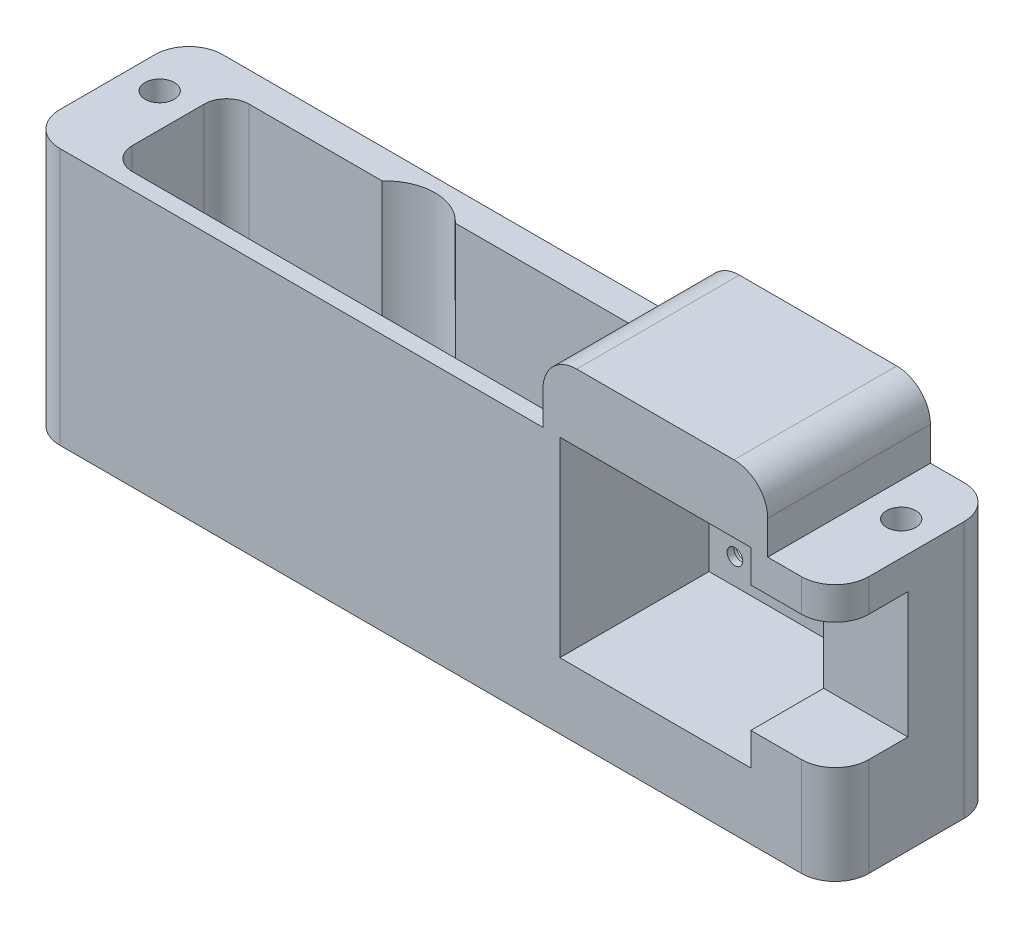
SolidWorks part; units mm, degrees
ref_plane "Front Plane" through (0, 0, 0) normal (0, 0, 1) x (1, 0, 0)
ref_plane "Top Plane" through (0, 0, 0) normal (0, 1, 0) x (1, 0, 0)
ref_plane "Right Plane" through (0, 0, 0) normal (1, 0, 0) x (0, 0, -1)
sketch "Sketch1" plane through (0, 0, 0) normal (0, 0, 1) x (1, 0, 0)
  line L1 (-90, 28.6) -> (90, 28.6)
  line L2 (-90, 28.6) -> (-90, -28.6)
  line L3 (-90, -28.6) -> (90, -28.6)
  line L4 (90, 28.6) -> (90, -28.6)
  line L5 (-90, 28.6) -> (90, -28.6) construction
  line L6 (-90, -28.6) -> (90, 28.6) construction
  line L7 (25, 28.6) -> (75, 28.6)
  line L8 (25, 28.6) -> (25, 43.6)
  line L9 (25, 43.6) -> (75, 43.6)
  line L10 (75, 28.6) -> (75, 43.6)
  point P0 (0, 0)
  dimension "D1" = 180
  dimension "D2" = 57.2
  dimension "D3" = 15
  dimension "D4" = 15
  dimension "D5" = 50
extrude "Boss-Extrude1" add sketch "Sketch1" along normal blind 36.2 contours L4 L1 L2 L3 | L1 L10 L9 L8 region at (0, 0, 0) region at (50, 36.1, 0)
sketch "Sketch2" plane through (0, -28.6, 0) normal (0, -1, 0) x (1, 0, 0)
  line L0 (-90, 36.2) -> (-90, 0) construction
  line L1 (-90, 0) -> (90, 0) construction
  line L3 (-82.5, 14) -> (82.5, 14) construction
  line L4 (-37.9069, 8.3431) -> (-26.5931, 8.3431) construction
  line L5 (-37.9069, 8.3431) -> (-37.9069, 19.6569) construction
  line L6 (-37.9069, 19.6569) -> (-26.5931, 19.6569) construction
  line L7 (-26.5931, 8.3431) -> (-26.5931, 19.6569) construction
  line L8 (-37.9069, 8.3431) -> (-26.5931, 19.6569) construction
  line L9 (-37.9069, 19.6569) -> (-26.5931, 8.3431) construction
  circle A0 centre (-82.5, 14) radius 3.25
  circle A1 centre (82.5, 14) radius 3.25
  circle A2 centre (-32.25, 14) radius 5.75
  circle A3 centre (-32.25, 14) radius 11
  circle A4 centre (-37.9069, 19.6569) radius 1.75
  circle A5 centre (-26.5931, 19.6569) radius 1.75
  circle A6 centre (-26.5931, 8.3431) radius 1.75
  circle A7 centre (-37.9069, 8.3431) radius 1.75
  dimension "D1" = 6.5
  dimension "D4" = 6.5
  dimension "D7" = 11.5
  dimension "D8" = 22
  dimension "D9" = 3.5
  dimension "D11" = 50.25
  dimension "D2" = 7.5
  dimension "D3" = 14
  dimension "D5" = 14
  dimension "D6" = 114.75
  dimension "D10" = 8
extrude "Cut-Extrude1" cut sketch "Sketch2" against normal up to surface (57.2 mm away) contours A0 | A2 | A4 | A5 | A7 | A6 | A1 region at (-82.5, -28.6, 14) region at (-32.25, -28.6, 14) up to face at (-32.5, 28.6, 18.1)
fillet "Fillet1" radius 7.5 4 edges at (90, 0, 0) (90, 0, 36.2) (-90, 0, 0) (-90, 0, 36.2)
sketch "Sketch3" plane through (0, 28.6, 0) normal (0, 1, 0) x (1, 0, 0)
  line L0 (-82.5, -36.2) -> (25, -36.2) construction
  line L1 (-70, -6.5931) -> (25, -6.5931)
  line L2 (-75, -11.5931) -> (-75, -27.6)
  line L3 (-70, -32.6) -> (25, -32.6)
  line L4 (25, -6.5931) -> (25, -32.6)
  line L5 (25, -36.2) -> (25, 0) construction
  circle A0 centre (-37.9069, -8.3431) radius 1.75 construction
  circle A1 centre (-82.5, -14) radius 3.25 construction
  arc A2 (-75, -27.6) -> (-70, -32.6) centre (-70, -27.6) ccw
  arc A3 (-70, -6.5931) -> (-75, -11.5931) centre (-70, -11.5931) ccw
  circle A4 centre (-32.25, -14) radius 11
  circle M6 centre (-26.5931, -8.3431) radius 1.75
  circle M7 centre (-37.9069, -19.6569) radius 1.75
  circle M8 centre (-32.25, -14) radius 5.75
  circle M9 centre (-26.5931, -19.6569) radius 1.75
  circle M10 centre (-37.9069, -8.3431) radius 1.75
  line M16 (25, -36.2) -> (25, 0)
  dimension "D4" = 5
  dimension "D5" = 22
  dimension "D1" = 26.0069
  dimension "D2" = 3.6
  dimension "D3" = 7.5
extrude "Cut-Extrude3" cut sketch "Sketch3" against normal offset from surface (52.2 mm away) 5 contours L1 A4 | L1 A4 M6 M10 M7 M9 M8 | A4 L1 A3 L2 A2 L3 M16 region at (-55.1913, 28.6, 7.6264) region at (-32.25, 28.6, 5.1337) region at (-39.1447, 28.6, 6.88) up to face at (-82.5, -28.6, 10.75)
sketch "Sketch4" plane through (0, 0, 36.2) normal (0, 0, 1) x (1, 0, 0)
  line L0 (-82.5, 28.6) -> (25, 28.6) construction
  line L1 (28.75, 28.6) -> (71.25, 28.6)
  line L2 (28.75, 28.6) -> (28.75, -13.9)
  line L3 (28.75, -13.9) -> (71.25, -13.9)
  line L4 (71.25, 28.6) -> (71.25, -13.9)
  line L5 (50, 7.35) -> (75, 28.6) construction
  line L6 (50, 7.35) -> (25, 28.6) construction
  line L7 (28.75, 7.35) -> (71.25, 7.35) construction
  line L8 (34.5, 22.85) -> (65.5, -8.15) construction
  line L9 (34.5, 22.85) -> (34.5, -8.15) construction
  circle A0 centre (50, 7.35) radius 11.25
  circle A5 centre (34.5, 22.85) radius 1.75
  circle A6 centre (65.5, 22.85) radius 1.75
  circle A7 centre (65.5, -8.15) radius 1.75
  circle A8 centre (34.5, -8.15) radius 1.75
  dimension "D5" = 22.5
  dimension "D6" = 3.5
  dimension "D3" = 2
  dimension "D7" = 31
  dimension "D8" = 31
  dimension "D1" = 42.5
  dimension "D2" = 42.5
  dimension "D4" = 2
extrude "Cut-Extrude4" cut sketch "Sketch4" against normal blind 33.2
extrude "Cut-Extrude5" cut sketch "Sketch4<3>" against normal up to surface (36.2 mm away) contours A5 | A0 | A8 | A7 | A6 up to face at (25, 18.05, 0)
sketch "Sketch4<3>" plane through (0, 0, 36.2) normal (0, 0, 1) x (1, 0, 0) same geometry as "Sketch4"
fillet "Fillet2" radius 7.5 2 edges at (75, 43.6, 18.1) (25, 43.6, 18.1)
sketch "Sketch8" plane through (0, 0, 0) normal (0, 0, -1) x (-1, 0, 0)
  circle A0 centre (-65.5, 22.85) radius 3
  circle A1 centre (-34.5, 22.85) radius 3
  circle A2 centre (-34.5, -8.15) radius 3
  circle A3 centre (-65.5, -8.15) radius 3
  circle A4 centre (-34.5, -8.15) radius 1.75 construction
  circle A5 centre (-65.5, -8.15) radius 1.75 construction
  circle A6 centre (-65.5, 22.85) radius 1.75 construction
  dimension "D1" = 6
extrude "Cut-Extrude8" cut sketch "Sketch8" against normal blind 1.5
sketch "Sketch7" plane through (0, 0, 36.2) normal (0, 0, 1) x (1, 0, 0)
  line L0 (71.25, 28.6) -> (28.75, 28.6) construction
  line L2 (50, 36.1) -> (50, -21.4) construction
  line L4 (28.75, 7.35) -> (71.25, 7.35) construction
  line L5 (28.75, 28.6) -> (28.75, -13.9) construction
  line L6 (71.25, -13.9) -> (71.25, 28.6) construction
  circle A0 centre (50, -21.4) radius 3.25
  circle A1 centre (50, 36.1) radius 3.25
  point P6 (50, -21.4)
  point P8 (50, 7.35)
  dimension "D1" = 6.5
  dimension "D4" = 6.5
  dimension "D2" = 7.5
extrude "Cut-Extrude7" cut sketch "Sketch7" against normal up to surface (36.2 mm away) up to face at (62.5, -8.15, 0)
extrude "Boss-Extrude3" add sketch "Sketch7<2>" against normal blind 22.4
sketch "Sketch7<2>" plane through (0, 0, 36.2) normal (0, 0, 1) x (1, 0, 0) same geometry as "Sketch7"
sketch "Sketch9" plane through (90, 0, 0) normal (1, 0, 0) x (0, 0, -1)
  line L0 (-36.2, -28.6) -> (-36.2, 28.6) construction
  line L1 (-36.2, 21.35) -> (-20, 21.35)
  line L2 (-36.2, 21.35) -> (-36.2, -6.65)
  line L3 (-36.2, -6.65) -> (-20, -6.65)
  line L4 (-20, 21.35) -> (-20, -6.65)
  line L5 (0, 28.6) -> (0, -28.6) construction
  line L6 (-28.7, 28.6) -> (-7.5, 28.6) construction
  dimension "D1" = 20
  dimension "D2" = 28
  dimension "D3" = 7.25
extrude "Cut-Extrude9" cut sketch "Sketch9" against normal up to surface (18.75 mm away) up to face at (71.25, 7.35, 19.6)
